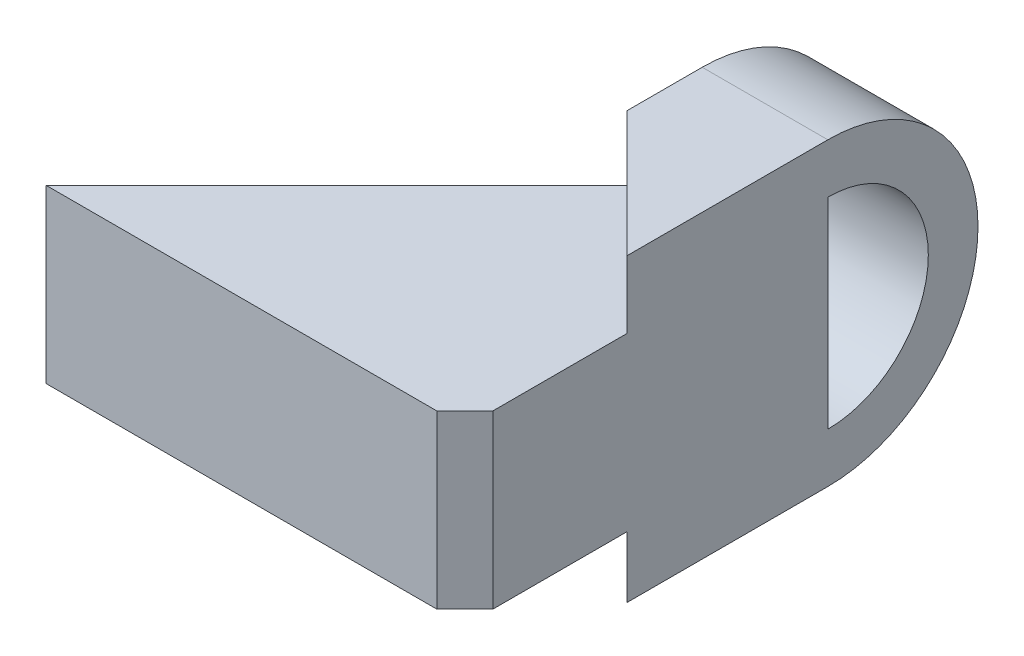
SolidWorks part; units mm, degrees
ref_plane "Płaszczyzna przednia" through (0, 0, 0) normal (0, 0, 1) x (1, 0, 0)
ref_plane "Płaszczyzna górna" through (0, 0, 0) normal (0, 1, 0) x (1, 0, 0)
ref_plane "Płaszczyzna prawa" through (0, 0, 0) normal (1, 0, 0) x (0, 0, -1)
sketch "Szkic1" plane through (0, 0, 0) normal (1, 0, 0) x (0, 0, -1)
  circle A0 centre (0, 0) radius 8
  circle A1 centre (0, 0) radius 11.9555
extrude "Dodanie-wyciągnięcie1" add sketch "Szkic1" along normal blind 10
sketch "Szkic2" plane through (0, 0, 0) normal (0, 0, 1) x (1, 0, 0)
  line L1 (0, 11.9555) -> (10, 11.9555)
  line L2 (0, 11.9555) -> (0, -11.9555)
  line L3 (0, -11.9555) -> (10, -11.9555)
  line L4 (10, 11.9555) -> (10, -11.9555)
extrude "Dodanie-wyciągnięcie2" add sketch "Szkic2" along normal blind 21
chamfer "Sfazowanie1" distance 15 angle 45 1 edges at (0, 0, 21)
sketch "Szkic4" plane through (-3, 0, 3) normal (-0.7071, 0, 0.7071) x (0.7071, 0, 0.7071)
  line L1 (6.8135, 6.5956) -> (15.9264, 6.5956)
  line L2 (6.8135, 6.5956) -> (6.8135, -7.0736)
  line L3 (6.8135, -7.0736) -> (15.9264, -7.0736)
  line L4 (15.9264, 6.5956) -> (15.9264, -7.0736)
extrude "Dodanie-wyciągnięcie4" add sketch "Szkic4" along normal blind 33
sketch "Szkic5" plane through (11.2616, 0, 11.2616) normal (0.7071, 0, 0.7071) x (0.7071, 0, -0.7071)
  line L1 (-37.2426, 6.5956) -> (4.1689, 6.5956)
  line L2 (-37.2426, 6.5956) -> (-37.2426, -7.0736)
  line L3 (-37.2426, -7.0736) -> (4.1689, -7.0736)
  line L4 (4.1689, 6.5956) -> (4.1689, -7.0736)
extrude "Dodanie-wyciągnięcie5" add sketch "Szkic5" along normal blind 10 and the other way blind 12
sketch "Szkic6" plane through (0, 6.5956, 0) normal (0, 1, 0) x (1, 0, 0)
  line L1 (10, -4.1043) -> (26.083, -4.1043)
  line L2 (10, -4.1043) -> (10, -31.3106)
  line L3 (10, -31.3106) -> (26.083, -31.3106)
  line L4 (26.083, -4.1043) -> (26.083, -31.3106)
extrude "Wytnij-wyciągnięcie1" cut sketch "Szkic6" against normal through all
sketch "Szkic7" plane through (0, 6.5956, 0) normal (0, 1, 0) x (1, 0, 0)
  line L0 (-23.7705, -28.8986) -> (9.4162, -28.8986)
  line L1 (-8.0018, -44.6672) -> (-23.5582, -29.1109) construction
  line L2 (9.4162, -28.8986) -> (9.4162, -47.9194)
  line L3 (9.4162, -47.9194) -> (-20.1488, -47.9194)
  line L4 (-20.1488, -47.9194) -> (-23.7705, -28.8986)
extrude "Wytnij-wyciągnięcie2" cut sketch "Szkic7" against normal through all
